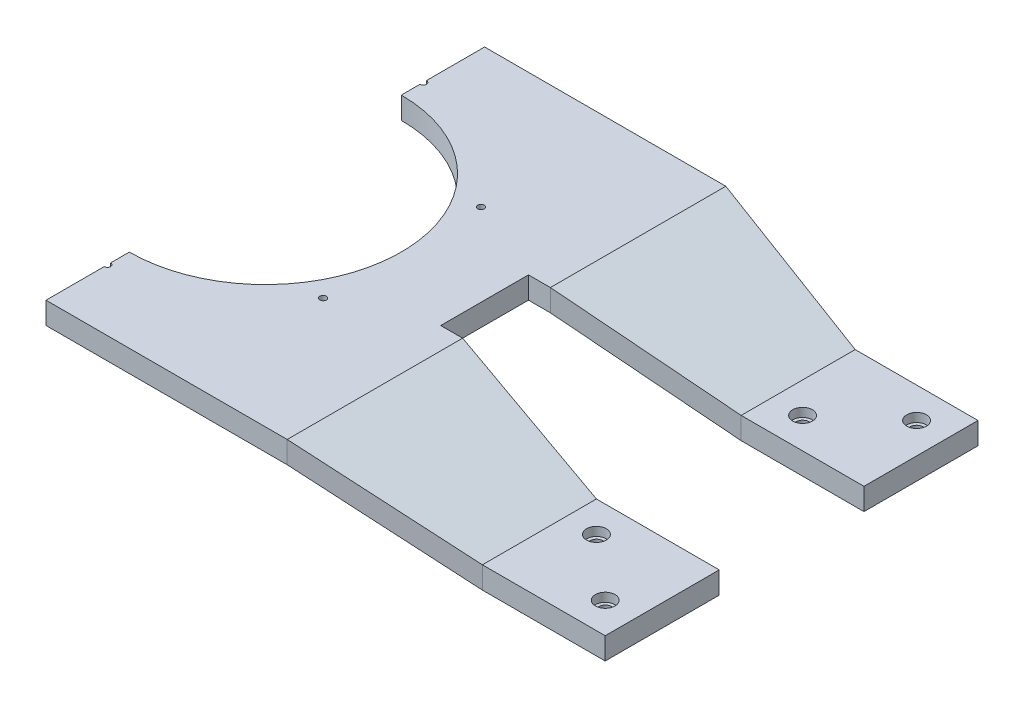
SolidWorks part; units mm, degrees
ref_plane "前视基准面" through (0, 0, 0) normal (0, 0, 1) x (1, 0, 0)
ref_plane "上视基准面" through (0, 0, 0) normal (0, 1, 0) x (1, 0, 0)
ref_plane "右视基准面" through (0, 0, 0) normal (1, 0, 0) x (0, 0, -1)
other "Configuration Table"
sketch "草图1" plane through (0, 0, 0) normal (0, 1, 0) x (1, 0, 0)
  line L1 (0, -50) -> (50, -50)
  line L2 (0, -50) -> (0, 50)
  line L3 (0, 50) -> (50, 50)
  line L4 (50, -50) -> (50, 50)
  line L11 (92, 42.5) -> (120, 42.5)
  line L12 (92, 42.5) -> (92, -42.5)
  line L13 (92, -42.5) -> (120, -42.5)
  line L14 (120, 42.5) -> (120, -42.5)
  line L15 (92, 16.5) -> (120, 16.5)
  line L16 (92, 16.5) -> (92, -16.5)
  line L17 (92, -16.5) -> (120, -16.5)
  line L18 (120, 16.5) -> (120, -16.5)
  point P0 (0, 0)
  point P11 (92, 0)
  point P16 (92, 0)
  dimension "D1" = 50
  dimension "D2" = 100
  dimension "D3" = 33
  dimension "D4" = 85
  dimension "D5" = 28
  dimension "D6" = 120
extrude "凸台-拉伸1" add sketch "草图1" along normal blind 5 contours L12 L15 L14 L11 | L17 L12 L13 L14 region at (106, 0, -29.5) region at (106, 0, 29.5)
extrude "凸台-拉伸2" add sketch "草图1<12>" along normal blind 5 from offset 10 separate body contours L3 L4 L1 L2
sketch "草图1<12>" plane through (0, 0, 0) normal (0, 1, 0) x (1, 0, 0) same geometry as "草图1"
sketch "草图2" plane through (50, 0, 0) normal (1, 0, 0) x (0, 0, -1)
  line L0 (50, 15) -> (50, 10) construction
  line L1 (50, 15) -> (10, 15)
  line L2 (50, 15) -> (50, 10)
  line L3 (50, 10) -> (10, 10)
  line L4 (10, 15) -> (10, 10)
  line L5 (-50, 15) -> (50, 15) construction
  line L6 (-50, 10) -> (50, 10) construction
  line L7 (-50, 15) -> (-50, 10) construction
  line L8 (-50, 15) -> (-10, 15)
  line L9 (-50, 15) -> (-50, 10)
  line L10 (-50, 10) -> (-10, 10)
  line L11 (-10, 15) -> (-10, 10)
  dimension "D1" = 40
extrude "凸台-拉伸3" add sketch "草图2" along normal blind 5
loft "放样5" add section face at (55, 12.5, 30) section face at (92, 2.5, 29.5) connector at (55, 15, 50) connector at (92, 5, 42.5)
loft "放样6" add section face at (55, 12.5, -30) section face at (92, 2.5, -29.5) connector at (55, 15, -10) connector at (92, 5, -16.5)
sketch "草图3" plane through (0, 5, 0) normal (0, 1, 0) x (1, 0, 0)
  line L0 (92, 42.5) -> (120, 42.5) construction
  line L1 (120, 42.5) -> (120, 16.5) construction
  line L2 (92, 42.5) -> (92, 16.5) construction
  line L3 (92, 16.5) -> (120, 16.5) construction
  line L6 (92, -42.5) -> (120, -42.5) construction
  line L7 (92, -16.5) -> (120, -16.5) construction
  circle A0 centre (113, 35.5) radius 1.5
  circle A1 centre (99, 23.5) radius 2.25
  circle A2 centre (99, 23.5) radius 1.5
  circle A3 centre (113, 35.5) radius 2.25
  circle A4 centre (113, -35.5) radius 2.25
  circle A5 centre (113, -35.5) radius 1.5
  circle A6 centre (99, -23.5) radius 2.25
  circle A7 centre (99, -23.5) radius 1.5
  dimension "D1" = 3
  dimension "D2" = 4.5
  dimension "D3" = 7
  dimension "D4" = 7
  dimension "D5" = 7
  dimension "D6" = 7
  dimension "D7" = 7
  dimension "D8" = 7
extrude "切除-拉伸1" cut sketch "草图3" against normal through all contours A5 | A7 | A2 | A0
extrude "切除-拉伸2" cut sketch "草图3<3>" against normal blind 2 contours A6 | A4 | A1 | A3
sketch "草图3<3>" plane through (0, 5, 0) normal (0, 1, 0) x (1, 0, 0) same geometry as "草图3"
sketch "草图4" plane through (0, 15, 0) normal (0, 1, 0) x (1, 0, 0)
  circle A0 centre (0, 36) radius 0.75
  circle A1 centre (31.1769, 18) radius 0.75
  circle A2 centre (31.1769, -18) radius 0.75
  circle A3 centre (0, -36) radius 0.75
  dimension "D1" = 1.5
extrude "切除-拉伸3" cut sketch "草图4" against normal blind 4 contours A0 | A1 | A2 | A3
sketch "草图5" plane through (0, 15, 0) normal (0, 1, 0) x (1, 0, 0)
  circle A0 centre (0, 0) radius 31
  dimension "D1" = 62
extrude "切除-拉伸4" cut sketch "草图5" against normal through all
sketch "草图6" plane through (0, 0, 0) normal (1, 0, 0) x (0, 0, -1)
  line L1 (-200, -100) -> (200, -100)
  line L2 (-200, -100) -> (-200, 100)
  line L3 (-200, 100) -> (200, 100)
  line L4 (200, -100) -> (200, 100)
  line L5 (-200, -100) -> (200, 100) construction
  line L6 (-200, 100) -> (200, -100) construction
  point P0 (0, 0)
  dimension "D1" = 400
  dimension "D2" = 200
mirror "镜向1" about plane through (0, 0, 0) normal (1, 0, 0) of bodies 153
extrude "切除-拉伸5" cut sketch "草图6" against normal through all
